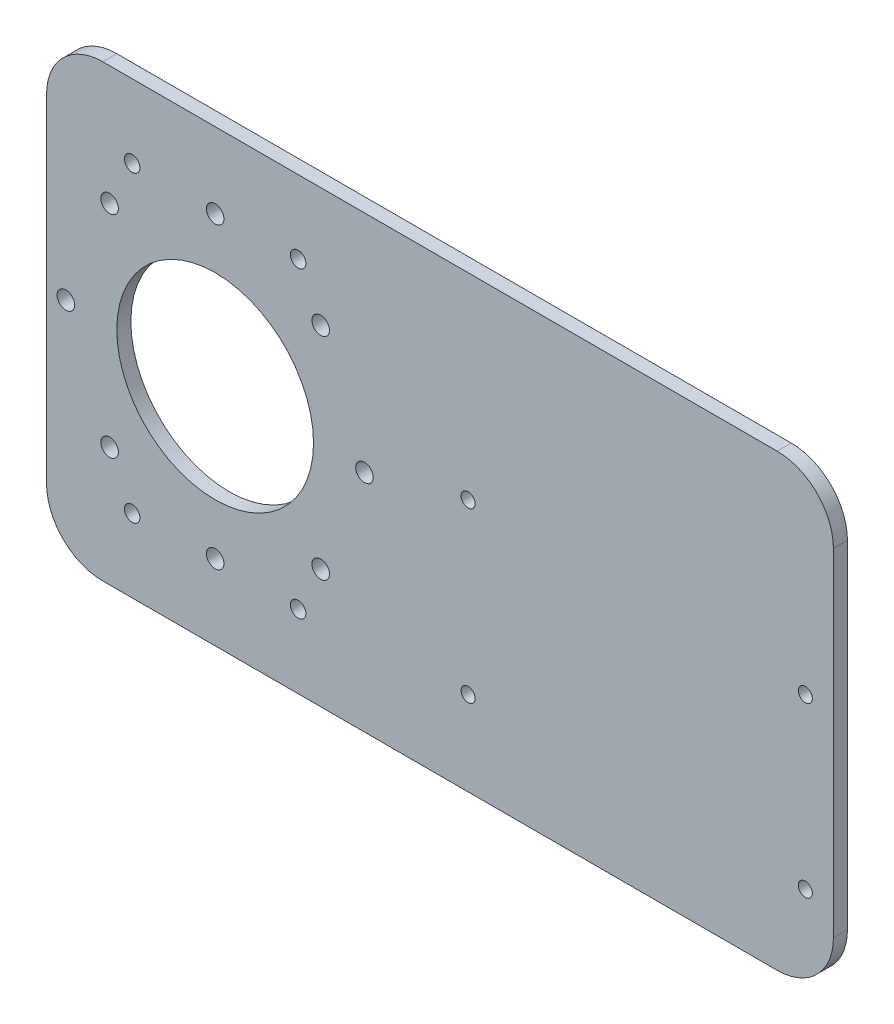
SolidWorks part; units mm, degrees
material "6061 Alloy"
ref_plane "Front Plane" through (0, 0, 0) normal (0, 0, 1) x (1, 0, 0)
ref_plane "Top Plane" through (0, 0, 0) normal (0, 1, 0) x (1, 0, 0)
ref_plane "Right Plane" through (0, 0, 0) normal (1, 0, 0) x (0, 0, -1)
sketch "Sketch1" plane through (0, 0, 0) normal (0, 0, 1) x (1, 0, 0)
  line L1 (0, 0) -> (355.6, 0)
  line L2 (0, 0) -> (0, 203.2)
  line L3 (0, 203.2) -> (355.6, 203.2)
  line L4 (355.6, 0) -> (355.6, 203.2)
  dimension "D1" = 203.2
  dimension "D2" = 355.6
extrude "Boss-Extrude1" add sketch "Sketch1" along normal blind 6.35
sketch "Sketch2" plane through (0, 0, 6.35) normal (0, 0, 1) x (1, 0, 0)
  line L0 (355.6, 203.2) -> (0, 203.2) construction
  line L1 (0, 203.2) -> (0, 0) construction
  circle A0 centre (76.2, 101.6) radius 76.2
  circle A1 centre (76.2, 101.6) radius 44.45
  circle A2 centre (143.6688, 101.6) radius 3.9687
  circle A10 centre (123.9076, 53.8924) radius 3.9687
  circle A11 centre (76.2, 34.1312) radius 3.9687
  circle A12 centre (28.4924, 53.8924) radius 3.9687
  circle A13 centre (8.7312, 101.6) radius 3.9687
  circle A14 centre (28.4924, 149.3076) radius 3.9688
  circle A15 centre (76.2, 169.0687) radius 3.9687
  circle A16 centre (123.9076, 149.3076) radius 3.9688
  point P9 (0, 0)
  point P10 (0, 0)
  point P11 (0, 0)
  point P26 (0, 0)
  point P27 (0, 0)
  point P28 (0, 0)
  point P29 (0, 0)
  dimension "D1" = 152.4
  dimension "D4" = 88.9
  dimension "D5" = 7.9375
  dimension "D6" = 67.4688
  dimension "D2" = 101.6
  dimension "D3" = 76.2
  dimension "D7" = 101.6
  dimension "D8" = 8
extrude "Cut-Extrude1" cut sketch "Sketch2" against normal blind 76.2 contours A2 | A1 | A10 | A12 | A13 | A11 | A14 | A15 | A16
sketch "Sketch3" plane through (0, 0, 6.35) normal (0, 0, 1) x (1, 0, 0)
  line L0 (76.2, 170.1) -> (76.2, 33.1) construction
  line L1 (38.6994, 170.1) -> (113.7006, 170.1) construction
  line L2 (38.6994, 170.1) -> (38.6994, 33.1) construction
  line L3 (38.6994, 33.1) -> (113.7006, 33.1) construction
  line L4 (113.7006, 170.1) -> (113.7006, 33.1) construction
  line L5 (113.7006, 101.6) -> (38.6994, 101.6)
  line L6 (0, 203.2) -> (0, 0) construction
  line L7 (355.6, 203.2) -> (0, 203.2) construction
  circle A0 centre (38.6994, 170.1) radius 3.5001
  circle A1 centre (113.7006, 170.1) radius 3.5001
  circle A2 centre (113.7006, 33.1) radius 3.5001
  circle A3 centre (38.6994, 33.1) radius 3.5001
  point P16 (0, 0)
  point P17 (0, 0)
  dimension "D3" = 7.0002
  dimension "D4" = 76.2
  dimension "D1" = 75.0011
  dimension "D2" = 137
  dimension "D5" = 101.6
extrude "Cut-Extrude2" cut sketch "Sketch3" against normal blind 6.35 contours A0 | A1 | A2 | A3 region at (38.6994, 170.1, 6.35) region at (113.7006, 170.1, 6.35) region at (113.7006, 33.1, 6.35) region at (38.6994, 33.1, 6.35)
fillet "Fillet1" radius 25.4 4 edges at (0, 203.2, 3.175) (0, 0, 3.175) (355.6, 0, 3.175) (355.6, 203.2, 3.175)
sketch "Sketch5" plane through (0, 0, 0) normal (0, 0, -1) x (-1, 0, 0)
  line L0 (-341.8766, 76.2) -> (-161.8766, 76.2) construction
  line L1 (-25.4, 0) -> (-330.2, 0) construction
  line L2 (-355.6, 25.4) -> (-355.6, 177.8) construction
  circle A0 centre (-342.9, 114.3) radius 3.175
  circle A1 centre (-190.5, 114.3) radius 3.175
  circle A2 centre (-190.5, 38.1) radius 3.175
  circle A3 centre (-342.9, 38.1) radius 3.175
  dimension "D3" = 38.1
  dimension "D1" = 152.4
  dimension "D2" = 76.2
  dimension "D4" = 12.7
extrude "Cut-Extrude4" cut sketch "Sketch5" against normal blind 6.35
